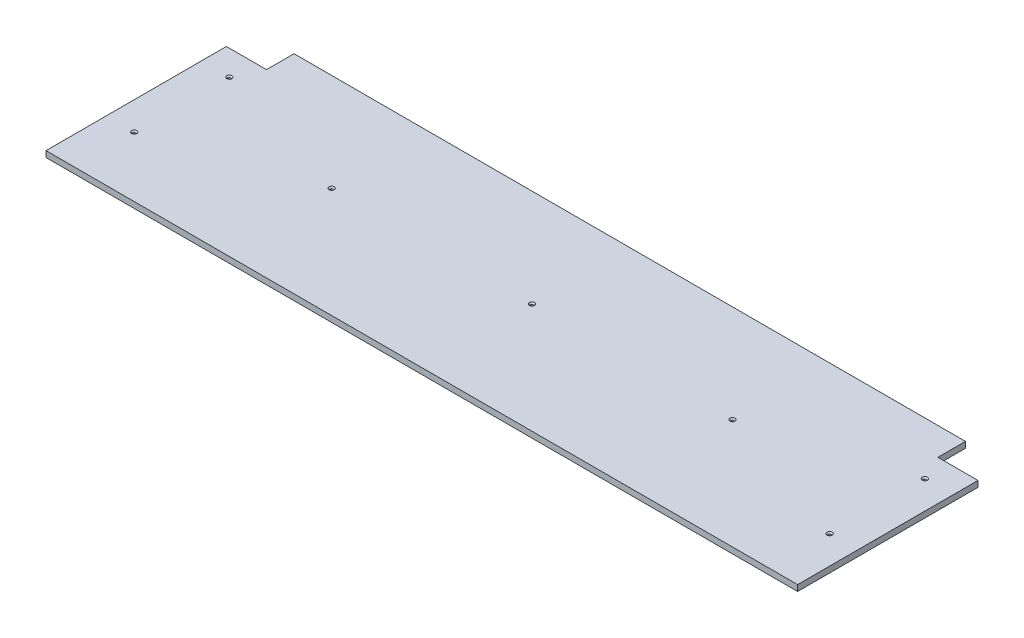
SolidWorks part; units mm, degrees
ref_plane "Front Plane" through (0, 0, 0) normal (0, 0, 1) x (1, 0, 0)
ref_plane "Top Plane" through (0, 0, 0) normal (0, 1, 0) x (1, 0, 0)
ref_plane "Right Plane" through (0, 0, 0) normal (1, 0, 0) x (0, 0, -1)
sketch "Sketch1" plane through (0, 0, 0) normal (0, 1, 0) x (1, 0, 0)
  line L1 (750, -207.5) -> (-750, -207.5)
  line L2 (750, -207.5) -> (750, 207.5)
  line L3 (750, 207.5) -> (-750, 207.5)
  line L4 (-750, -207.5) -> (-750, 207.5)
  line L5 (750, -207.5) -> (-750, 207.5) construction
  line L6 (750, 207.5) -> (-750, -207.5) construction
  point P0 (0, 0)
  dimension "D1" = 1500
  dimension "D2" = 415
extrude "RawMaterial" add sketch "Sketch1" along normal blind 12
hole_wizard "CSK for M5 Flat Head Machine Screw1" positions "Sketch3" profile "Sketch4" countersink size "M5" standard "ANSI Metric" end condition through all
sketch "Sketch3" plane through (0, 12, 0) normal (0, -1, 0) x (-1, 0, 0)
  line L6 (-750, -207.5) -> (-750, 207.5) construction
  line L7 (-750, 207.5) -> (750, 207.5) construction
  point P0 (-694, 102.5)
  point P2 (-694, -87.5)
  point P4 (-400, 12.5)
  point P6 (400, 12.5)
  point P8 (694, -87.5)
  point P10 (694, 102.5)
  point P50 (0, 12.5)
  dimension "D1" = 190
  dimension "D2" = 295
  dimension "D3" = 100
  dimension "D4" = 800
  dimension "D5" = 350
  dimension "D6" = 56
  dimension "D7" = 1444
sketch "Sketch4" plane through (694, 12, -102.5) normal (1, 0, 0) x (0, 0, 1)
  line L0 (0, 0) -> (0, 12)
  line L1 (0, 12) -> (2.6, 12)
  line L2 (2.6, 12) -> (2.6, 2.6)
  line L3 (2.6, 2.6) -> (5.2, 0)
  line L5 (5.2, 0) -> (0, 0)
  line L6 (-2.6, 2.6) -> (-5.2, 0) construction
  line L11 (0, -6.35) -> (0, 107.95) construction
  dimension "Thru Hole Dia." = 5.2
  dimension "Thru Hole Depth" = 12
  dimension "Near C'Sink Dia." = 10.4
  dimension "Near C'Sink Angle" = 90
sketch "Sketch5" plane through (0, 0, 0) normal (0, -1, 0) x (1, 0, 0)
  line L0 (-750, -152.5) -> (-670, -152.5)
  line L1 (-750, -207.5) -> (-750, 207.5) construction
  line L2 (670, -152.5) -> (670, -207.5)
  line L4 (750, -152.5) -> (670, -152.5)
  line L5 (750, 207.5) -> (750, -207.5) construction
  line L6 (750, -207.5) -> (-750, -207.5) construction
  line L7 (-670, -152.5) -> (-670, -207.5)
  line M10 (-750, 207.5) -> (-750, -207.5)
  line M11 (-750, -207.5) -> (750, -207.5)
  line M12 (750, -207.5) -> (750, 207.5)
  dimension "D1" = 80
  dimension "D2" = 55
extrude "Frame Slots" cut sketch "Sketch5" against normal through all contours L7 L0 M10 M11 | L4 L2 M12 M11 region at (710, 0, -180) region at (-710, 0, -180)
